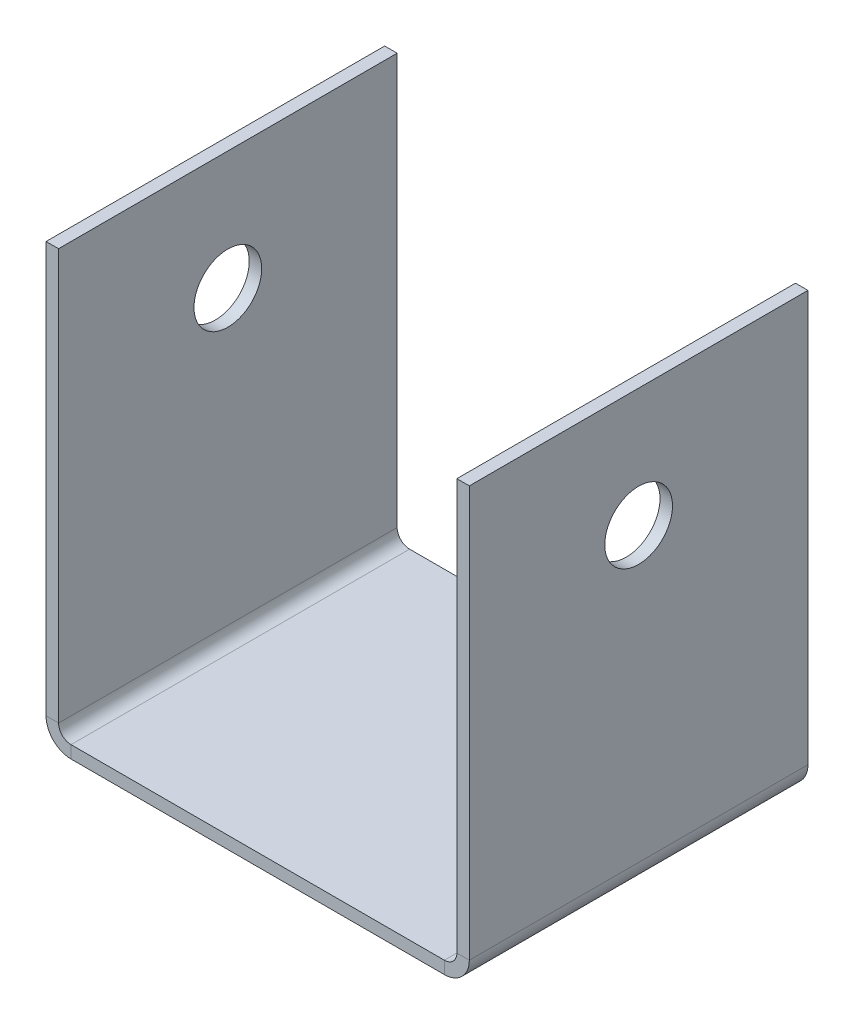
SolidWorks part; units mm, degrees
note: The reader was unsure of these and kept them because the rebuilt part matched: flange length of "Edge-Flange1".
ref_plane "Front Plane" through (0, 0, 0) normal (0, 0, 1) x (1, 0, 0)
ref_plane "Top Plane" through (0, 0, 0) normal (0, 1, 0) x (1, 0, 0)
ref_plane "Right Plane" through (0, 0, 0) normal (1, 0, 0) x (0, 0, -1)
sketch "Sketch1" plane through (0, 0, 0) normal (0, 1, 0) x (1, 0, 0)
  line L1 (-12.5, -10) -> (12.5, -10)
  line L2 (-12.5, -10) -> (-12.5, 10)
  line L3 (-12.5, 10) -> (12.5, 10)
  line L4 (12.5, -10) -> (12.5, 10)
  line L5 (-12.5, -10) -> (12.5, 10) construction
  line L6 (-12.5, 10) -> (12.5, -10) construction
  point P0 (0, 0)
  dimension "D1" = 20
  dimension "D2" = 25
base flange "Base-Flange1" sketch "Sketch1" thickness 0.7366 reverse thickness direction no parameters "D1"=0.7366
edge flange "Edge-Flange1" sketch "Sketch10" flange profiles "Sketch10", "Sketch11" flange angle 90 flange length 25 flange position material inside bend radius 0.7366 thickness 0.7366 relief rectangular parameters "D6"=10, "D8"=1
sketch "Sketch10" plane through (12.5, 0, 0) normal (1, 0, 0) x (0, 0, -1)
  line L0 (-10, 0) -> (10, 0) construction
  line L1 (-10, 0) -> (10, 0)
  line L2 (-10, 0) -> (-10, 25)
  line L3 (-10, 25) -> (10, 25)
  line L4 (10, 25) -> (10, 0)
sketch "Sketch11" plane through (-12.5, 0, 0) normal (-1, 0, 0) x (0, 0, 1)
  line L0 (-10, 0) -> (10, 0) construction
  line L1 (-10, 0) -> (10, 0)
  line L2 (-10, 0) -> (-10, 25)
  line L3 (-10, 25) -> (10, 25)
  line L4 (10, 25) -> (10, 0)
bend "EdgeBend1" bend radius 0.7366 bend angle 90 parameters "D5"=1
bend "EdgeBend2" bend radius 0.7366 bend angle 90 parameters "D5"=2
hole_wizard "Ø4.0 (4) Diameter Hole1" positions "Sketch13" profile "Sketch12" hole size "Ø4.0" standard "ISO" end condition through all
sketch "Sketch13" plane through (12.5, 0, 0) normal (1, 0, 0) x (0, 0, -1)
  point P0 (0, 17.9834)
  dimension "D1" = 18.72
sketch "Sketch12" plane through (12.5, 17.9834, 0) normal (0, 1, 0) x (0, 0, -1)
  line L0 (0, 0) -> (0, 25)
  line L1 (0, 25) -> (2, 25)
  line L2 (2, 25) -> (2, 0)
  line L5 (2, 0) -> (0, 0)
  line L11 (0, -6.35) -> (0, 107.95) construction
  dimension "Thru Hole Dia." = 4
  dimension "Thru Hole Depth" = 25
sketch "Bend-Lines1" plane through (0, 0, 0) normal (0, 1, 0) x (1, 0, 0)
sketch "Bounding-Box1" plane through (0, 0, 0) normal (0, 1, 0) x (1, 0, 0)
sheet metal parameters "Sheet-Metal1" thickness 0.7366 parameters "D1"=0.7366
flat pattern "Flat-Pattern1" [suppressed]
sketch "Bend-Lines2" plane through (0, 0, 0) normal (0, 1, 0) x (1, 0, 0)
sketch "Bounding-Box2" [suppressed] plane through (0, 0, 0) normal (0, 1, 0) x (1, 0, 0)
sheet metal parameters "Sheet-Metal2" thickness 0.7366 parameters "D1"=0.7366
flat pattern "Flat-Pattern1" [suppressed]
sketch "Bend-Lines2" plane through (0, 0, 0) normal (0, 1, 0) x (1, 0, 0)
sketch "Bounding-Box2" [suppressed] plane through (0, 0, 0) normal (0, 1, 0) x (1, 0, 0)
bend of the flat pattern "Flatten-<EdgeBend1>1"
bend of the flat pattern "Flatten-<EdgeBend2>1"
sheet metal parameters "Sheet-Metal3" thickness 0.7366 parameters "D1"=0.7366
flat pattern "Flat-Pattern1" [suppressed]
sketch "Bend-Lines2" plane through (0, 0, 0) normal (0, 1, 0) x (1, 0, 0)
sketch "Bounding-Box2" [suppressed] plane through (0, 0, 0) normal (0, 1, 0) x (1, 0, 0)
bend of the flat pattern "Flatten-<EdgeBend1>1"
bend of the flat pattern "Flatten-<EdgeBend2>1"
